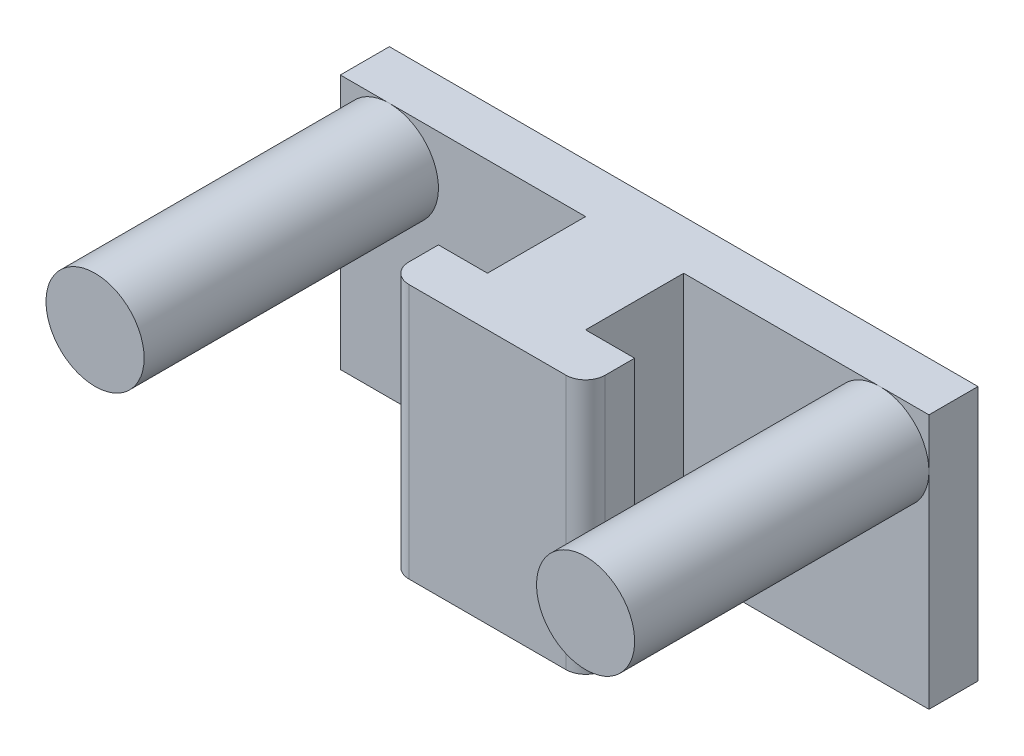
SolidWorks part; units mm, degrees
ref_plane "Front Plane" through (0, 0, 0) normal (0, 0, 1) x (1, 0, 0)
ref_plane "Top Plane" through (0, 0, 0) normal (0, 1, 0) x (1, 0, 0)
ref_plane "Right Plane" through (0, 0, 0) normal (1, 0, 0) x (0, 0, -1)
sketch "Sketch1" plane through (0, 0, 0) normal (0, 1, 0) x (1, 0, 0)
  line L0 (10, 0) -> (-10, 0)
  line L1 (-10, 0) -> (-10, 5)
  line L2 (-10, 5) -> (-5, 5)
  line L3 (-5, 5) -> (-5, 15)
  line L4 (-5, 15) -> (-30, 15)
  line L5 (-30, 15) -> (-30, 20)
  line L6 (-30, 20) -> (30, 20)
  line L7 (0, 20) -> (0, 0)
  line L8 (30, 15) -> (30, 20)
  line L9 (5, 15) -> (30, 15)
  line L10 (5, 5) -> (5, 15)
  line L11 (10, 5) -> (5, 5)
  line L12 (10, 0) -> (10, 5)
  dimension "D1" = 10
  dimension "D2" = 5
  dimension "D3" = 10
  dimension "D4" = 30
  dimension "D5" = 5
  dimension "D6" = 5
extrude "Boss-Extrude1" add sketch "Sketch1" along normal blind 26 contours L7 L6 L5 L4 L3 L2 L1 L0 | L0 L12 L11 L10 L9 L8 L6 L7 region at (5, 0, -0.3606) region at (-5, 0, -0.3606)
sketch "Sketch2" plane through (0, 0, -15) normal (0, 0, 1) x (1, 0, 0)
  line L1 (-5, 26) -> (-30, 26) construction
  line L2 (-30, 26) -> (-30, 0) construction
  circle A0 centre (-25, 21) radius 5
  dimension "D1" = 10
extrude "Boss-Extrude2" add sketch "Sketch2" along normal blind 30 contours A0
mirror "Mirror1" about plane through (0, 0, 0) normal (1, 0, 0) of "Boss-Extrude2"
fillet "Fillet1" radius 2 2 edges at (10, 13, 0) (-10, 13, 0)
equation "\"shaftDiam\" = 20mm"
equation "\"keyW\" = 8mm"
equation "\"keyL\" = 10mm"
equation "\"clearance\" = .8mm"
equation "\"handleShaftLen\" = 60mm"
equation "\"panelH\" = 80mm"
equation "\"panelW\" = 110mm"
equation "\"D1@Sketch1\"=\"shaftDiam\"/2"
equation "\"D2@Sketch1\"=\"shaftDiam\"/4"
equation "\"D3@Sketch1\"=\"shaftDiam\"/2"
equation "\"D4@Sketch1\"= \"shaftDiam\" * 1.5"
equation "\"D5@Sketch1\"=\"shaftDiam\"/4"
equation "\"D6@Sketch1\"=\"shaftDiam\"/4"
equation "\"D1@Boss-Extrude1\"= \"shaftDiam\" + \"handleShaftLen\" / 10"
equation "\"D1@Sketch2\"=\"shaftDiam\"/2"
equation "\"D1@Boss-Extrude2\"=\"shaftDiam\"*1.5"
equation "\"D1@Fillet1\"=\"shaftDiam\"/10"
